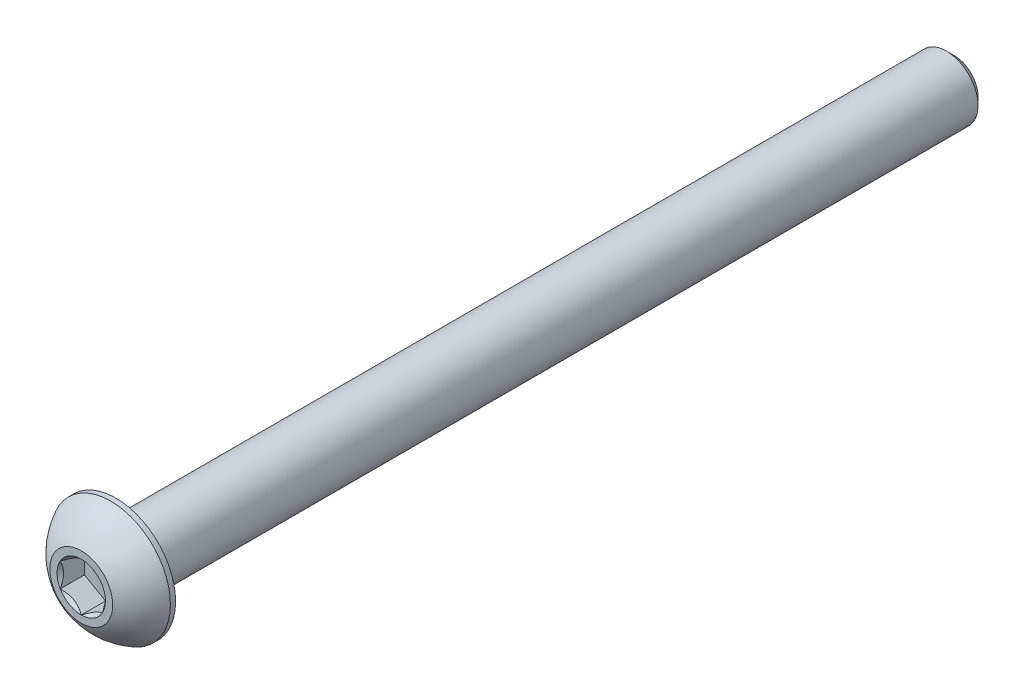
SolidWorks part; units mm, degrees
ref_plane "Front" through (0, 0, 0) normal (0, 0, 1) x (1, 0, 0)
ref_plane "Top" through (0, 0, 0) normal (0, 1, 0) x (1, 0, 0)
ref_plane "Right" through (0, 0, 0) normal (1, 0, 0) x (0, 0, -1)
sketch "Sketch1" plane through (0, 0, 0) normal (1, 0, 0) x (0, 0, -1)
  line L2 (1.65, 1.5) -> (41.65, 1.5)
  line L3 (41.65, 1.5) -> (41.65, 0)
  line L4 (41.65, 0) -> (1.65, 0)
  line L6 (1.4025, 2.85) -> (1.65, 2.85) construction
  line L7 (41.65, 1.5) -> (41.65, -1.5) construction
  line L8 (0, 0) -> (1.65, 0) construction
  line L9 (1.65, 2.85) -> (1.65, -2.85) construction
  line L11 (1.65, 1.5) -> (1.65, 0)
  line L13 (0, 1) -> (0, -1) construction
  line L14 (0, 1) -> (0, 1.5) construction
  arc A3 (0, 1.5) -> (1.4025, 2.85) centre (2.7948, 0) cw construction
  dimension "D1" = 0.2475
revolve "Revolve1" add sketch "Sketch1" angle 360 mid plane about L4
sketch "Sketch3" plane through (0, 0, -41.65) normal (0, 0, -1) x (-1, 0, 0)
  circle A0 centre (0, 0) radius 1.5
curve "Helix/Spiral1" pitch 0.5 height 40.5 turns 81
chamfer "Chamfer1" distance 0.375 angle 45 1 edges at (0, 1.5, -41.65)
sketch "Sketch7" plane through (0, 0, 0) normal (1, 0, 0) x (0, 0, -1)
  line L6 (1.4025, 2.85) -> (1.65, 2.85) construction
  line L8 (0, 0) -> (1.65, 0) construction
  line L11 (1.65, 2.85) -> (1.65, -2.85) construction
  line L12 (1.4025, 2.85) -> (1.65, 2.85)
  line L13 (0, 0) -> (1.65, 0)
  line L14 (0, 1) -> (0, -1) construction
  line L15 (1.65, 2.85) -> (1.65, 0)
  line L16 (0, 1.5) -> (0, 0)
  arc A2 (1.4025, 2.85) -> (0, 1.5) centre (2.7948, 0) ccw construction
  arc A3 (1.4025, 2.85) -> (0, 1.5) centre (2.7948, 0) ccw
revolve "Revolve2" add sketch "Sketch7" angle 360 mid plane about L13
sketch "Sketch5" plane through (0, 0, 0) normal (0, 0, 1) x (1, 0, 0)
  line L1 (1, -0.5774) -> (1, 0.5774)
  line L2 (1, 0.5774) -> (0, 1.1547)
  line L3 (0, 1.1547) -> (-1, 0.5774)
  line L4 (-1, 0.5774) -> (-1, -0.5774)
  line L5 (-1, -0.5774) -> (0, -1.1547)
  line L6 (0, -1.1547) -> (1, -0.5774)
  circle A0 centre (0, 0) radius 1 construction
extrude "Cut-Extrude2" cut sketch "Sketch5" against normal blind 1.155
sketch "Sketch6" plane through (0, 0, 0) normal (0, 0, 1) x (1, 0, 0)
  circle A0 centre (0, 0) radius 1.1547
extrude "Cut-Extrude3" cut sketch "Sketch6" against normal blind 1.155 draft 45
sketch "Sketch2" plane through (0, 0, 0) normal (1, 0, 0) x (0, 0, -1)
  line L0 (41.275, 1.5) -> (41.7125, 1.5)
  line L1 (41.7125, 1.5) -> (41.525, 1.1752)
  line L2 (41.525, 1.1752) -> (41.4625, 1.1752)
  line L3 (41.4625, 1.1752) -> (41.275, 1.5)
  line L4 (41.3687, 1.3376) -> (41.6187, 1.3376) construction
  dimension "D1" = 60
  dimension "D2" = 0.0625
  dimension "D3" = 0.25
sweep "Cut-Sweep1" [suppressed] cut profiles "Sketch2" path "Helix/Spiral1"
sketch "Sketch10" plane through (0, 0, 0) normal (1, 0, 0) x (0, 0, -1)
  line L0 (41.65, 1.5) -> (41.65, -1.5) construction
  point P0 (40.9, -1.5)
  dimension "D1" = 0.75
ref_axis "Center Axis 1" through (0, 0, -8.1113) along (0, 0, 1)
ref_plane "Contact Plane 1" through (0, 0, -1.65) normal (0, 0, -1) x (-1, 0, 0)
ref_plane "Contact Plane 2" through (0, 0, 0) normal (0, 0, 1) x (1, 0, 0)
equation "\"D3@Helix/Spiral1\" = \"Lg@Sketch1\" + \"D4@Helix/Spiral1\""
equation "\"D2@Sketch2\" = \"D4@Helix/Spiral1\" * .125"
equation "\"D3@Sketch2\" = \"D4@Helix/Spiral1\" * .5"
equation "\"D1@Chamfer1\" = \"D4@Helix/Spiral1\" * .75"
equation "\"D1@Cut-Extrude2\" = \"Head Ht@Sketch1\" * .7"
equation "\"D1@Sketch1\" = \"Head Ht@Sketch1\" * .15"
equation "\"D1@Sketch10\" = \"D4@Helix/Spiral1\" * 1.5"
equation "\"D1@Cut-Extrude3\" = \"D1@Cut-Extrude2\""
